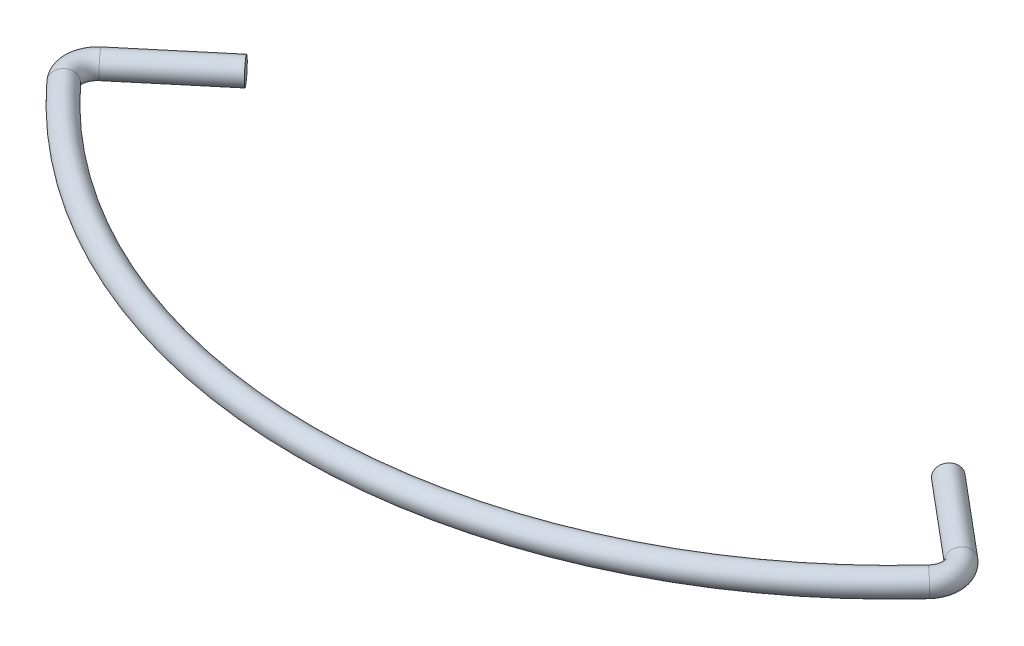
SolidWorks part; units mm, degrees
ref_plane "Front Plane" through (0, 0, 0) normal (0, 0, 1) x (1, 0, 0)
ref_plane "Top Plane" through (0, 0, 0) normal (0, 1, 0) x (1, 0, 0)
ref_plane "Right Plane" through (0, 0, 0) normal (1, 0, 0) x (0, 0, -1)
sketch "Overhead Sketch" plane through (0, 0, 0) normal (0, 1, 0) x (1, 0, 0)
  line L0 (0, 675) -> (0, -675) construction
  line L1 (0, 0) -> (517.08, -433.8816) construction
  line L2 (0, 0) -> (-517.08, -433.8816) construction
  line L3 (517.08, -433.8816) -> (539.5721, -452.7548)
  line L4 (-517.08, -433.8816) -> (-539.5721, -452.7548)
  line L5 (704.0417, -211.0693) -> (330.1183, -656.6939) construction
  circle A0 centre (0, 0) radius 675 construction
  arc A1 (-542.4285, -495.9802) -> (542.4285, -495.9802) centre (0, 0) ccw
  arc A2 (-542.4285, -495.9802) -> (-539.5721, -452.7548) centre (-520.2885, -475.7361) cw
  arc A3 (539.5721, -452.7548) -> (542.4285, -495.9802) centre (520.2885, -475.7361) cw
  point P11 (-563.0427, -472.4489)
  point P14 (563.0427, -472.4489)
  point P17 (517.08, -433.8816)
  dimension "D1" = 1350
  dimension "D3" = 30
  dimension "D4" = 60
  dimension "D2" = 100
ref_plane "Reference Plane" through (0, 0, 433.8816) normal (0, 0, 1) x (1, 0, 0)
sketch "Plane Definition Sketch" plane through (0, 0, 433.8816) normal (0, 0, 1) x (1, 0, 0)
  line L0 (517.08, 50) -> (517.08, -50) construction
  point P2 (517.08, 0)
  dimension "D1" = 100
ref_plane "Cross Section Plane" through (517.08, 0, 433.8816) normal (0.766, 0, 0.6428) x (0.6428, 0, -0.766)
sketch "Left Cross Section Sketch" plane through (517.08, 0, 433.8816) normal (0.766, 0, 0.6428) x (0.6428, 0, -0.766)
  circle A0 centre (0, 0) radius 15
  dimension "D1" = 30
sweep "Bar Sweep" add profiles "Left Cross Section Sketch" path "Overhead Sketch"
sketch "Right Cross Section Sketch" plane through (-517.08, 0, 433.8816) normal (0.766, 0, -0.6428) x (-0.6428, 0, -0.766)
  circle A0 centre (0, 0) radius 15
  circle A1 centre (0, 0) radius 15 construction
extrude "Right Joint Extrude" add sketch "Right Cross Section Sketch" along normal blind 100
extrude "Left Joint Extrude" add sketch "Left Cross Section Sketch<2>" against normal blind 100
sketch "Left Cross Section Sketch<2>" plane through (517.08, 0, 433.8816) normal (0.766, 0, 0.6428) x (0.6428, 0, -0.766) same geometry as "Left Cross Section Sketch"
